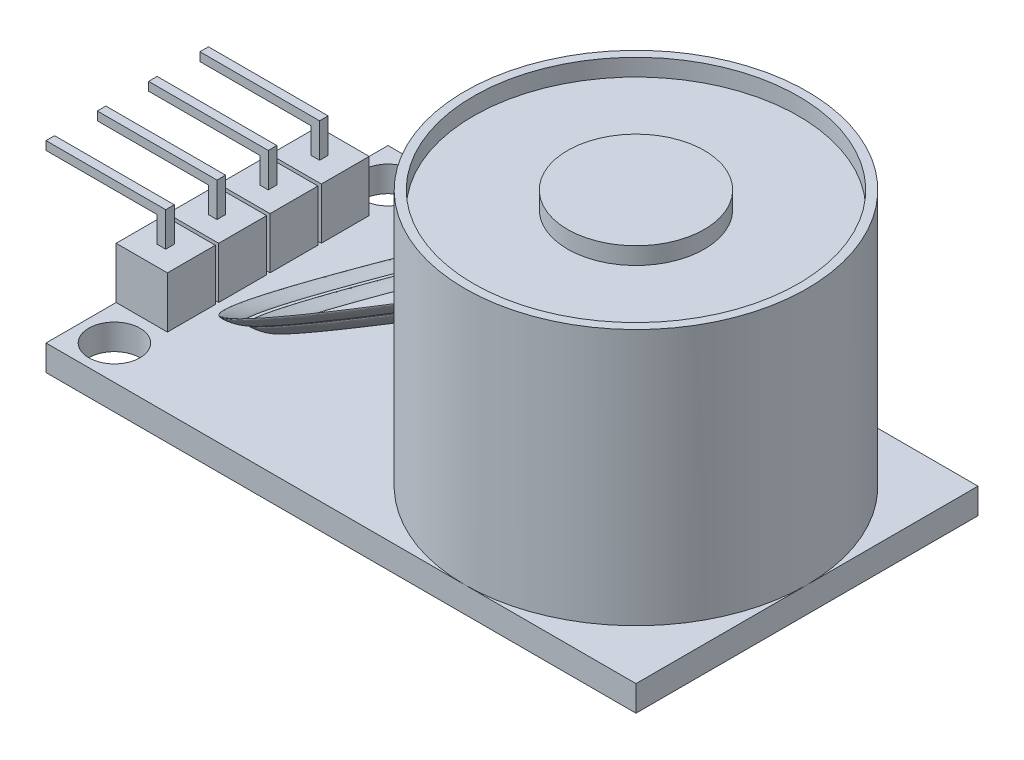
SolidWorks part; units mm, degrees
ref_plane "정면" through (0, 0, 0) normal (0, 0, 1) x (1, 0, 0)
ref_plane "윗면" through (0, 0, 0) normal (0, 1, 0) x (1, 0, 0)
ref_plane "우측면" through (0, 0, 0) normal (1, 0, 0) x (0, 0, -1)
sketch "스케치1" plane through (0, 0, 0) normal (0, 1, 0) x (1, 0, 0)
  line L1 (-17.25, 10) -> (17.25, 10)
  line L2 (-17.25, 10) -> (-17.25, -10)
  line L3 (-17.25, -10) -> (17.25, -10)
  line L4 (17.25, 10) -> (17.25, -10)
  line L5 (-17.25, 10) -> (17.25, -10) construction
  line L6 (-17.25, -10) -> (17.25, 10) construction
  point P0 (0, 0)
  dimension "D1" = 34.5
  dimension "D2" = 20
extrude "보스-돌출1" add sketch "스케치1" along normal blind 1.5
sketch "스케치2" plane through (0, 1.5, 0) normal (0, 1, 0) x (1, 0, 0)
  line L0 (-17.25, 0) -> (17.25, 0) construction
  line L1 (-17.25, 10) -> (-17.25, -10) construction
  line L2 (17.25, -10) -> (17.25, 10) construction
  line L3 (17.25, 10) -> (-17.25, 10) construction
  circle A0 centre (-15.25, 8) radius 1.5
  circle A1 centre (-15.25, -8) radius 1.5
  dimension "D1" = 3
  dimension "D2" = 2
  dimension "D3" = 2
extrude "컷-돌출1" cut sketch "스케치2" against normal blind 1.5
sketch "스케치3" plane through (0, 1.5, 0) normal (0, 1, 0) x (1, 0, 0)
  line L0 (-17.25, -5.9) -> (-17.25, -3.1)
  line L1 (-17.25, 10) -> (-17.25, -10) construction
  line L3 (-14.25, 6) -> (-14.25, 3.1)
  line L5 (-17.25, -2.9) -> (-17.25, -0.1)
  line L6 (-14.25, -3.1) -> (-14.25, -5.9)
  line L7 (-14.25, -0.1) -> (-14.25, -2.9)
  line L8 (-17.25, 5.9) -> (-14.25, 5.9)
  line L9 (-17.25, 2.9) -> (-14.25, 2.9)
  line L10 (-17.25, -0.1) -> (-14.25, -0.1)
  line L11 (-17.25, -3.1) -> (-14.25, -3.1)
  line L12 (-14.25, -5.9) -> (-17.25, -5.9)
  line L13 (-17.25, 0.1) -> (-17.25, 2.9)
  line L14 (-17.25, 3.1) -> (-14.25, 3.1)
  line L15 (-17.25, 0.1) -> (-14.25, 0.1)
  line L16 (-17.25, -2.9) -> (-14.25, -2.9)
  line L17 (-14.25, 2.9) -> (-14.25, 0.1)
  line L18 (-17.25, 3.1) -> (-17.25, 6)
  point P5 (-17.25, 0)
  line M7 (-17.25, 10) -> (-17.25, -10)
extrude "보스-돌출2" add sketch "스케치3" along normal blind 3 separate body contours L14 L3 L8 M7 | L17 L9 L15 M7 | L16 L7 L10 M7 | L12 L6 L11 M7 region at (-15.75, 1.5, -4.5) region at (-15.75, 1.5, -1.5) region at (-15.75, 1.5, 1.5) region at (-15.75, 1.5, 4.5)
sketch "스케치4" plane through (0, 4.5, 0) normal (0, 1, 0) x (1, 0, 0)
  line L0 (-15.75, 5.9) -> (-15.75, 3.1) construction
  line L1 (-17.25, 5.9) -> (-14.25, 5.9) construction
  line L2 (-17.25, 3.1) -> (-14.25, 3.1) construction
  line L3 (-15.75, 3.1) -> (-15.75, 2.9) construction
  line L4 (-17.25, 2.9) -> (-14.25, 2.9) construction
  line L5 (-15.75, 2.9) -> (-15.75, 0.1) construction
  line L6 (-17.25, 0.1) -> (-14.25, 0.1) construction
  line L7 (-15.75, 0.1) -> (-15.75, -0.1) construction
  line L8 (-17.25, -0.1) -> (-14.25, -0.1) construction
  line L9 (-15.75, -0.1) -> (-15.75, -2.9) construction
  line L10 (-17.25, -2.9) -> (-14.25, -2.9) construction
  line L11 (-15.75, -2.9) -> (-15.75, -3.1) construction
  line L12 (-17.25, -3.1) -> (-14.25, -3.1) construction
  line L13 (-15.75, -3.1) -> (-15.75, -5.9) construction
  line L14 (-14.25, -5.9) -> (-17.25, -5.9) construction
  line L16 (-16, 4.75) -> (-15.5, 4.75)
  line L17 (-16, 4.75) -> (-16, 4.25)
  line L18 (-16, 4.25) -> (-15.5, 4.25)
  line L19 (-15.5, 4.75) -> (-15.5, 4.25)
  line L20 (-16, 4.75) -> (-15.5, 4.25) construction
  line L21 (-16, 4.25) -> (-15.5, 4.75) construction
  line L22 (-16, 1.75) -> (-15.5, 1.75)
  line L23 (-16, 1.75) -> (-16, 1.25)
  line L24 (-16, 1.25) -> (-15.5, 1.25)
  line L25 (-15.5, 1.75) -> (-15.5, 1.25)
  line L26 (-16, 1.75) -> (-15.5, 1.25) construction
  line L27 (-16, 1.25) -> (-15.5, 1.75) construction
  line L28 (-16, -1.25) -> (-15.5, -1.25)
  line L29 (-16, -1.25) -> (-16, -1.75)
  line L30 (-16, -1.75) -> (-15.5, -1.75)
  line L31 (-15.5, -1.25) -> (-15.5, -1.75)
  line L32 (-16, -1.25) -> (-15.5, -1.75) construction
  line L33 (-16, -1.75) -> (-15.5, -1.25) construction
  line L34 (-16, -4.25) -> (-15.5, -4.25)
  line L35 (-16, -4.25) -> (-16, -4.75)
  line L36 (-16, -4.75) -> (-15.5, -4.75)
  line L37 (-15.5, -4.25) -> (-15.5, -4.75)
  line L38 (-16, -4.25) -> (-15.5, -4.75) construction
  line L39 (-16, -4.75) -> (-15.5, -4.25) construction
  point P6 (-15.75, 4.5)
  point P29 (-15.75, 1.5)
  point P34 (-15.75, -1.5)
  point P39 (-15.75, -4.5)
  dimension "D1" = 0.5
  dimension "D2" = 0.5
  dimension "D3" = 0.5
  dimension "D4" = 0.5
  dimension "D5" = 0.5
  dimension "D6" = 0.5
  dimension "D7" = 0.5
  dimension "D8" = 0.5
extrude "보스-돌출3" add sketch "스케치4" along normal blind 2 separate body
sketch "스케치5" plane through (-16, 0, 0) normal (-1, 0, 0) x (0, 0, 1)
  line L0 (-4.25, 6.5) -> (-4.25, 4.5) construction
  line L1 (-4.75, 6.5) -> (-4.25, 6.5)
  line L2 (-4.75, 6.5) -> (-4.75, 6)
  line L3 (-4.75, 6) -> (-4.25, 6)
  line L4 (-4.25, 6.5) -> (-4.25, 6)
  line L5 (-1.25, 6.5) -> (-1.25, 4.5) construction
  line L6 (-1.75, 6.5) -> (-1.25, 6.5)
  line L7 (-1.75, 6.5) -> (-1.75, 6)
  line L8 (-1.75, 6) -> (-1.25, 6)
  line L9 (-1.25, 6.5) -> (-1.25, 6)
  line L10 (1.75, 6.5) -> (1.75, 4.5) construction
  line L11 (1.25, 6.5) -> (1.75, 6.5)
  line L12 (1.25, 6.5) -> (1.25, 6)
  line L13 (1.25, 6) -> (1.75, 6)
  line L14 (1.75, 6.5) -> (1.75, 6)
  line L15 (4.75, 6.5) -> (4.75, 4.5) construction
  line L16 (4.25, 6.5) -> (4.75, 6.5)
  line L17 (4.25, 6.5) -> (4.25, 6)
  line L18 (4.25, 6) -> (4.75, 6)
  line L19 (4.75, 6.5) -> (4.75, 6)
  dimension "D1" = 0.5
  dimension "D2" = 0.5
extrude "보스-돌출4" add sketch "스케치5" along normal blind 6.5
sketch "스케치6" plane through (0, 1.5, 0) normal (0, 1, 0) x (1, 0, 0)
  line L0 (17.25, 0) -> (-17.25, 0) construction
  line L1 (17.25, -10) -> (17.25, 10) construction
  line L2 (-17.25, 10) -> (-17.25, -10) construction
  line L3 (17.25, 10) -> (-17.25, 10) construction
  circle A1 centre (7.25, 0) radius 10
extrude "보스-돌출5" add sketch "스케치6" along normal blind 15 separate body
sketch "스케치7" plane through (0, 16.5, 0) normal (0, 1, 0) x (1, 0, 0)
  circle A0 centre (7.25, 0) radius 9.5
  circle A1 centre (7.25, 0) radius 4
  dimension "D1" = 19
  dimension "D2" = 8
extrude "컷-돌출2" cut sketch "스케치7" against normal blind 1
sketch "스케치8" plane through (0, 1.5, 0) normal (0, 1, 0) x (1, 0, 0)
  circle A0 centre (-10.5698, 5.129) radius 0.5
  circle A1 centre (-9.3183, 5.129) radius 0.5
  dimension "D1" = 1
sketch3d "3D스케치2"
  spline S0 degree 2 poles (-10.5698, 1.5, -5.129) (-14.1348, 3.9873, 12.9608) (-1.5948, 8.4853, 4.6658) knots 0 0 0 1 1 1
  point P0 (-1.5948, 8.4853, 4.6658)
  point P1 (-9.0002, 5.2386, 7.0981)
sweep "스윕1" add profiles "스케치8" path "3D스케치2"
